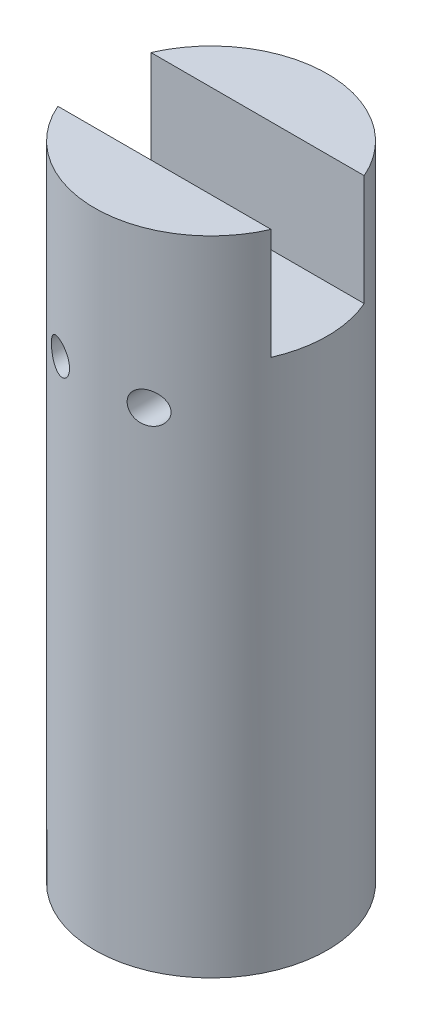
SolidWorks part; units mm, degrees
ref_plane "Front Plane" through (0, 0, 0) normal (0, 0, 1) x (1, 0, 0)
ref_plane "Top Plane" through (0, 0, 0) normal (0, 1, 0) x (1, 0, 0)
ref_plane "Right Plane" through (0, 0, 0) normal (1, 0, 0) x (0, 0, -1)
sketch "Sketch1" plane through (0, 0, 0) normal (0, 1, 0) x (1, 0, 0)
  circle A0 centre (0, 0) radius 26.25
  dimension "D1" = 52.5
extrude "Boss-Extrude1" add sketch "Sketch1" along normal blind 145
sketch "Sketch2" plane through (0, 145, 0) normal (0, 1, 0) x (1, 0, 0)
  line L5 (-24.0585, 10.5) -> (24.0585, 10.5)
  line L7 (-24.0585, -10.5) -> (24.0585, -10.5)
  line L9 (-24.0585, 10.5) -> (24.0585, -10.5) construction
  line L10 (-24.0585, -10.5) -> (24.0585, 10.5) construction
  circle A1 centre (0, 0) radius 26.25 construction
  arc A2 (-24.0585, 10.5) -> (-24.0585, -10.5) centre (-24.0585, 0) ccw
  arc A3 (24.0585, 10.5) -> (24.0585, -10.5) centre (24.0585, 0) cw
  point P0 (0, 0)
  point P9 (0, 0)
  dimension "D2" = 10.5
  dimension "D3" = 10.5
  dimension "D1" = 21
  dimension "D4" = 48.117
extrude "Cut-Extrude1" cut sketch "Sketch2" against normal blind 25
sketch "Sketch3" plane through (0, 0, 0) normal (0, 0, 1) x (1, 0, 0)
  line L0 (-10, 110) -> (10, 110) construction
  line L1 (26.25, 120) -> (24.0585, 120) construction
  circle A0 centre (-10, 110) radius 3.5
  circle A1 centre (10, 110) radius 3.5
  point P4 (0, 110)
  dimension "D1" = 7
  dimension "D2" = 7
  dimension "D3" = 10
  dimension "D4" = 20
extrude "Cut-Extrude2" cut sketch "Sketch3" against normal through all both and the other way through all
sketch "Sketch4" plane through (0, 0, 0) normal (0, -1, 0) x (1, 0, 0)
  circle A0 centre (0, 0) radius 3.95
  dimension "D1" = 7.9
extrude "Boss-Extrude2" add sketch "Sketch4" along normal blind 7
sketch "Sketch5" plane through (0, 0, 0) normal (0, -1, 0) x (1, 0, 0)
  circle A0 centre (0, 0) radius 5
  dimension "D1" = 10
extrude "Boss-Extrude3" add sketch "Sketch5" along normal blind 1
equation "\"Overall Diameter\"= 52.5"
equation "\"Front Slot Width\"= 21"
equation "\"Back Slot Width\"= 20.8"
equation "\"Slot Depth\"= 25"
equation "\"Bearing OD\"= 22.3"
equation "\"Bearing ID\"= 7.9"
equation "\"D1@Sketch1\"=\"Overall Diameter\""
equation "\"D1@Sketch2\"=\"Front Slot Width\""
equation "\"D3@Sketch2\"=10.5"
equation "\"D1@Cut-Extrude1\"=\"Slot Depth\""
equation "\"Bearing ID Depth\"= 7"
equation "\"Bearing ID Stopper\"= 10"
equation "\"Bearing ID Stopper Depth\"= 1"
equation "\"D1@Sketch4\"=\"Bearing ID\""
equation "\"D1@Boss-Extrude2\"=\"Bearing ID Depth\""
equation "\"D1@Sketch5\"=\"Bearing ID Stopper\""
equation "\"D1@Boss-Extrude3\"=\"Bearing ID Stopper Depth\""
